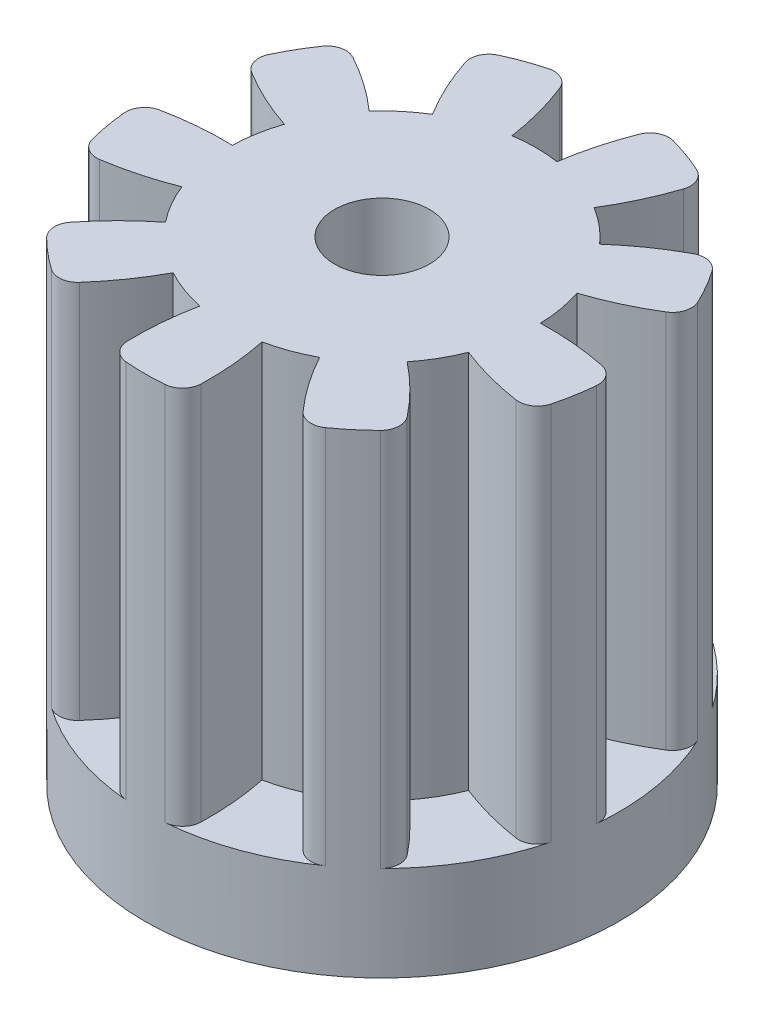
SolidWorks part; units mm, degrees
ref_plane "Front Plane" through (0, 0, 0) normal (0, 0, 1) x (1, 0, 0)
ref_plane "Top Plane" through (0, 0, 0) normal (0, 1, 0) x (1, 0, 0)
ref_plane "Right Plane" through (0, 0, 0) normal (1, 0, 0) x (0, 0, -1)
sketch "Sketch1" plane through (0, 0, 0) normal (0, 1, 0) x (1, 0, 0)
  circle A0 centre (0, 0) radius 1.25
  circle A1 centre (0, 0) radius 0.25
  dimension "D1" = 2.5
  dimension "D2" = 0.5
extrude "Boss-Extrude1" add sketch "Sketch1" along normal blind 2.5
sketch "Sketch2" plane through (0, 2.5, 0) normal (0, 1, 0) x (1, 0, 0)
  line L0 (0, 0) -> (0, 2.1618) construction
  line L1 (0, 0) -> (0.7463, 2.0506) construction
  line L2 (-0.1954, 1.1079) -> (0.1954, 1.1079) construction
  line L3 (0.1954, 1.1079) -> (0.5625, 0.9743) construction
  line L4 (-0.1185, 0.8038) -> (0, 0) construction
  line L5 (0, 0.5712) -> (-0.3247, 1.4632) construction
  circle A0 centre (0, 0) radius 1.25 construction
  circle A1 centre (0, 0) radius 1.125 construction
  circle A2 centre (0, 0) radius 1.25 construction
  circle A3 centre (0, 0) radius 1.25 construction
  circle A9 centre (0, 0) radius 0.8125 construction
  arc A10 (-0.2439, 1.226) -> (-0.1185, 0.8038) centre (-1.6516, 0.5779) cw
  arc A11 (0.2439, 1.226) -> (0.1185, 0.8038) centre (1.6516, 0.5779) ccw
  arc A12 (-0.2439, 1.226) -> (0.2439, 1.226) centre (0, 0) cw
  arc A13 (-0.1185, 0.8038) -> (0.1185, 0.8038) centre (0, 0) cw
  dimension "D1" = 2.25
  dimension "D2" = 2.5
  dimension "D4" = 1.625
  dimension "D3" = 20
  dimension "D5" = 20
extrude "Cut-Extrude1" cut sketch "Sketch2" against normal through all
pattern_circular "CirPattern1" count 9 over 360 about axis through (0, 2.5, 0) along (0, -1, 0) of "Cut-Extrude1"
fillet "Fillet1" radius 0.1 18 edges at (0.9749, 1.25, -0.7824) (0.2439, 1.25, -1.226) (0.6012, 1.25, -1.0959) (1.165, 1.25, -0.4531) (1.2497, 1.25, 0.0273) (0.9398, 1.25, 0.8242) (1.1837, 1.25, 0.4017) (0.1901, 1.25, 1.2355) (0.6485, 1.25, 1.0686) (-0.1901, 1.25, 1.2355) (-0.6485, 1.25, 1.0686) (-0.9398, 1.25, 0.8242) (-1.1837, 1.25, 0.4017) (-1.2497, 1.25, 0.0273) (-1.165, 1.25, -0.4531) (-0.9749, 1.25, -0.7824) (-0.2439, 1.25, -1.226) (-0.6012, 1.25, -1.0959)
sketch "Sketch3" plane through (0, 0, 0) normal (0, 1, 0) x (1, 0, 0)
  circle A0 centre (0, 0) radius 1.25
extrude "Boss-Extrude2" add sketch "Sketch3" along normal blind 0.5
